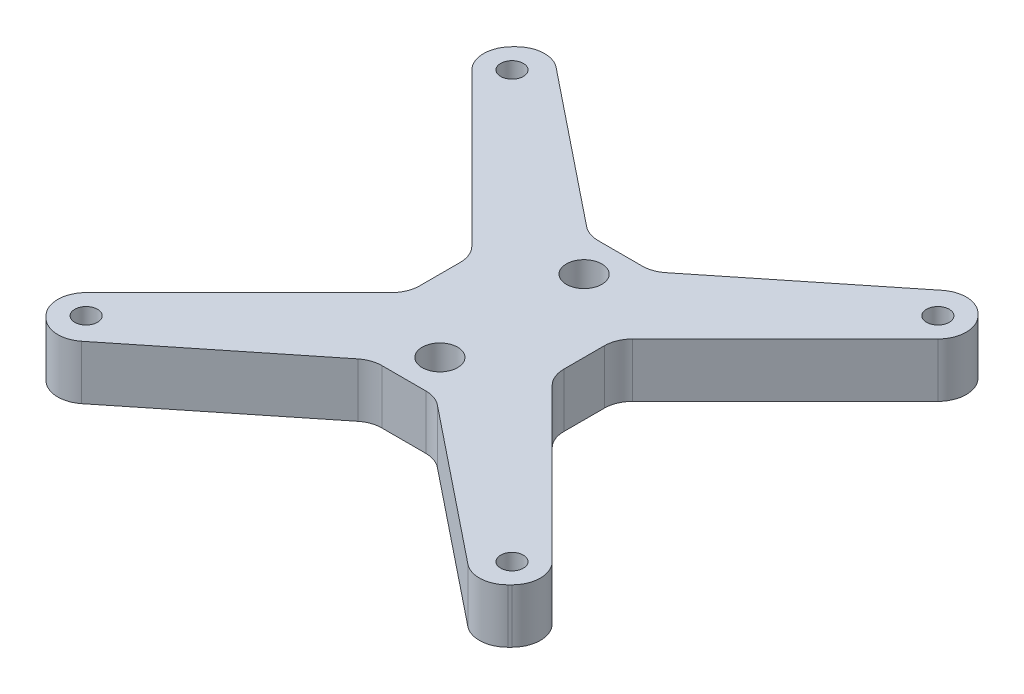
SolidWorks part; units mm, degrees
ref_plane "Front Plane" through (0, 0, 0) normal (0, 0, 1) x (1, 0, 0)
ref_plane "Top Plane" through (0, 0, 0) normal (0, 1, 0) x (1, 0, 0)
ref_plane "Right Plane" through (0, 0, 0) normal (1, 0, 0) x (0, 0, -1)
sketch "Sketch1" plane through (0, 0, 0) normal (0, 1, 0) x (1, 0, 0)
  line L4 (-37.5, -37.5) -> (37.5, 37.5) construction
  line L5 (37.5, -37.5) -> (-37.5, 37.5) construction
  line L6 (-37.5, 37.5) -> (37.5, 37.5) construction
  line L7 (-12.7, 5.6289) -> (-44.5711, 37.5)
  line L8 (-44.5711, 37.5) -> (-37.5, 44.5711)
  line L10 (-5.6289, 12.7) -> (5.6289, 12.7) construction
  line L11 (5.6289, 12.7) -> (37.5, 44.5711) construction
  line L12 (37.5, 44.5711) -> (44.5711, 37.5)
  line L13 (44.5711, 37.5) -> (12.7, 5.6289)
  line L14 (12.7, 5.6289) -> (12.7, -5.6289)
  line L15 (12.7, -5.6289) -> (44.5711, -37.5)
  line L16 (44.5711, -37.5) -> (37.5, -44.5711)
  line L17 (37.5, -44.5711) -> (5.6289, -12.7) construction
  line L18 (5.6289, -12.7) -> (-5.6289, -12.7) construction
  line L19 (-5.6289, -12.7) -> (-37.5, -44.5711) construction
  line L20 (-37.5, -44.5711) -> (-44.5711, -37.5)
  line L21 (-44.5711, -37.5) -> (-12.7, -5.6289)
  line L22 (-12.7, -5.6289) -> (-12.7, 5.6289)
  line L23 (0, 12.7) -> (0, -12.7) construction
  line L24 (-37.5, 44.5711) -> (-5.6289, 12.7) construction
  line L25 (37.5, 37.5) -> (41.0355, 41.0355) construction
  line L26 (37.5, -37.5) -> (41.0355, -41.0355) construction
  line L27 (-37.5, -37.5) -> (-41.0355, -41.0355) construction
  line L28 (-37.5, 37.5) -> (-41.0355, 41.0355) construction
  line L29 (-37.5, -37.5) -> (37.5, -37.5) construction
  line L30 (-5.6289, -12.7) -> (5.6289, -12.7) construction
  line L31 (-5.6289, -12.7) -> (-5.6289, -19.05) construction
  line L32 (5.6289, -12.7) -> (5.6289, -19.05) construction
  line L33 (-5.6289, -19.05) -> (5.6289, -19.05)
  line L34 (-5.6289, 12.7) -> (5.6289, 12.7) construction
  line L35 (-5.6289, 12.7) -> (-5.6289, 19.05) construction
  line L36 (5.6289, 12.7) -> (5.6289, 19.05) construction
  line L37 (-5.6289, 19.05) -> (5.6289, 19.05)
  line L38 (5.6289, 19.05) -> (37.5, 44.5711)
  line L39 (-37.5, 44.5711) -> (-5.6289, 19.05)
  line L40 (-37.5, -44.5711) -> (-5.6289, -19.05)
  line L41 (5.6289, -19.05) -> (37.5, -44.5711)
  circle A0 centre (37.5, 37.5) radius 2
  circle A1 centre (37.5, -37.5) radius 2
  circle A2 centre (-37.5, -37.5) radius 2
  circle A3 centre (-37.5, 37.5) radius 2
  circle A5 centre (0, 12.7) radius 3.125
  circle A6 centre (0, -12.7) radius 3.125
  point P1 (0, 0)
  point P28 (0, 0)
  dimension "D2" = 4
  dimension "D1" = 75
  dimension "D3" = 25.4
  dimension "D4" = 10
  dimension "D5" = 6.35
  dimension "5" = 5
  dimension "D9" = 25.4
extrude "Boss-Extrude1" add sketch "Sketch1" along normal blind 9.525
fillet "Fillet1" radius 5 16 edges at (12.7, 4.7625, -5.6289) (12.7, 4.7625, 5.6289) (44.5711, 4.7625, 37.5) (-44.5711, 4.7625, 37.5) (-12.7, 4.7625, 5.6289) (-44.5711, 4.7625, -37.5) (44.5711, 4.7625, -37.5) (-12.7, 4.7625, -5.6289) (5.6289, 4.7625, 19.05) (-5.6289, 4.7625, 19.05) (-37.5, 4.7625, 44.5711) (37.5, 4.7625, 44.5711) (37.5, 4.7625, -44.5711) (5.6289, 4.7625, -19.05) (-5.6289, 4.7625, -19.05) (-37.5, 4.7625, -44.5711)
